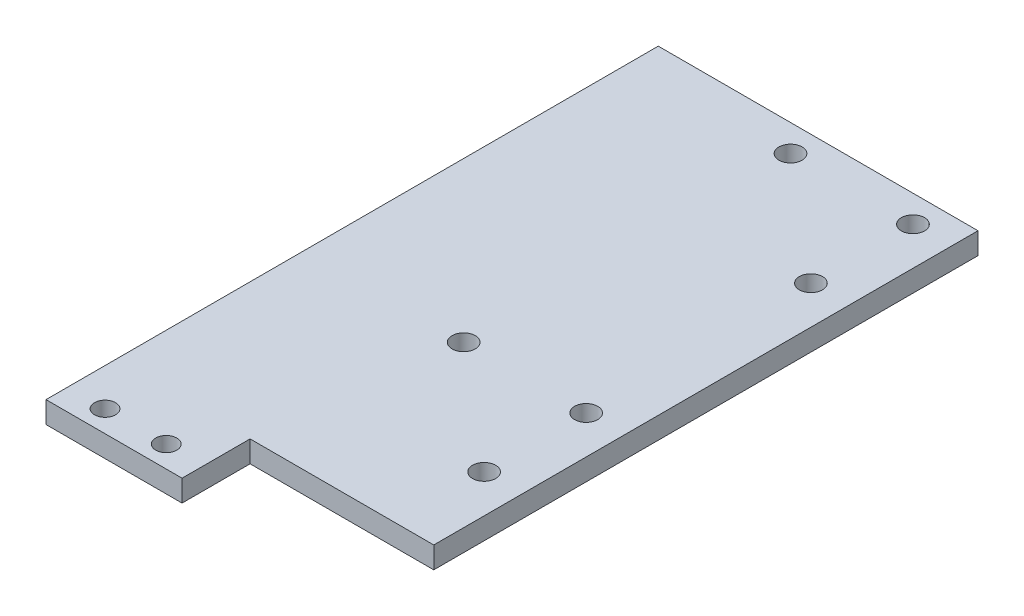
SolidWorks part; units mm, degrees
material "6061 Alloy"
ref_plane "Front Plane" through (0, 0, 0) normal (0, 0, 1) x (1, 0, 0)
ref_plane "Top Plane" through (0, 0, 0) normal (0, 1, 0) x (1, 0, 0)
ref_plane "Right Plane" through (0, 0, 0) normal (1, 0, 0) x (0, 0, -1)
sketch "Sketch1" plane through (0, 0, 0) normal (0, 1, 0) x (1, 0, 0)
  line L0 (0, 0) -> (0, 90)
  line L1 (0, 90) -> (47, 90)
  line L2 (47, 90) -> (47, 10)
  line L3 (47, 10) -> (20, 10)
  line L4 (20, 10) -> (20, 0)
  line L5 (0, 0) -> (20, 0)
  line L16 (20, 0) -> (20, 6.35) construction
  line L17 (14.5, 3.175) -> (5.5, 3.175) construction
  circle A5 centre (41.4, 86.0411) radius 1.7
  circle A6 centre (14.5, 3.175) radius 1.55
  circle A7 centre (23.4, 86.0411) radius 1.7
  circle A9 centre (5.5, 3.175) radius 1.55
  circle A12 centre (41.4, 23) radius 1.7 construction
  circle A13 centre (41.4, 38) radius 1.7 construction
  circle A14 centre (23.4, 38) radius 1.7 construction
  circle A15 centre (41.4, 23) radius 1.7
  circle A16 centre (41.4, 38) radius 1.7
  circle A17 centre (23.4, 38) radius 1.7
  circle A18 centre (41.4, 71.0411) radius 1.7
  point P20 (10, 3.175)
  point P21 (10, 0)
  dimension "D2" = 3.1
  dimension "D3" = 3.1
  dimension "D1" = 80
  dimension "D9" = 47
  dimension "D11" = 10
  dimension "D4" = 9
  dimension "D5" = 3.175
  dimension "D6" = 15
extrude "Boss-Extrude1" add sketch "Sketch1" along normal blind 3.175
equation "\"D3@Sketch1\"=\"D2@Sketch1\""
